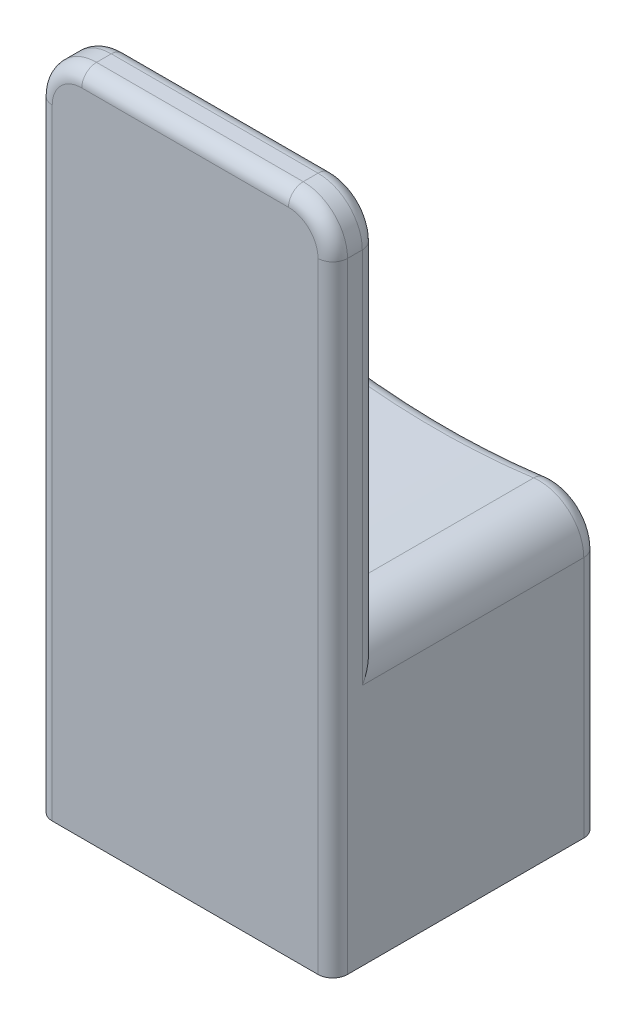
SolidWorks part; units mm, degrees
ref_plane "前视基准面" through (0, 0, 0) normal (0, 0, 1) x (1, 0, 0)
ref_plane "上视基准面" through (0, 0, 0) normal (0, 1, 0) x (1, 0, 0)
ref_plane "右视基准面" through (0, 0, 0) normal (1, 0, 0) x (0, 0, -1)
other "Configuration Table"
sketch "草图1" plane through (0, 0, 0) normal (0, 1, 0) x (1, 0, 0)
  circle A0 centre (0, 0) radius 3.9
  point P2 (1.8977, -1.4542)
  dimension "D1" = 7.8
extrude "凸台-拉伸1" add sketch "草图1" along normal blind 3.5
sketch "草图2" plane through (0, 3.5, 0) normal (0, 1, 0) x (1, 0, 0)
  line L1 (10, -7.5) -> (-10, -7.5)
  line L2 (10, -7.5) -> (10, 7.5)
  line L3 (10, 7.5) -> (-10, 7.5)
  line L4 (-10, -7.5) -> (-10, 7.5)
  line L5 (10, -7.5) -> (-10, 7.5) construction
  line L6 (10, 7.5) -> (-10, -7.5) construction
  point P0 (0, 0)
  dimension "D1" = 20
  dimension "D2" = 15
extrude "凸台-拉伸2" add sketch "草图2" along normal blind 20
sketch "草图3" plane through (0, 0, -7.5) normal (0, 0, -1) x (-1, 0, 0)
  line L0 (10, 23.5) -> (0, 20.5)
  line L1 (-10, 23.5) -> (10, 23.5) construction
  line L2 (0, 20.5) -> (-10, 23.5)
  line L3 (-10, 23.5) -> (-10, 3.5) construction
  line L4 (10, 23.5) -> (-10, 23.5)
  point P4 (0, 0)
  point P8 (0, 18.0324)
  point P9 (-10, 23.5)
  dimension "D1" = 3
extrude "切除-拉伸1" cut sketch "草图3" against normal through all
fillet "圆角1" radius 50 1 edges at (0, 20.5, 0)
fillet "圆角2" radius 3 2 edges at (-10, 23.5, 0) (10, 23.5, 0)
sketch "草图5" plane through (0, 0, 7.5) normal (0, 0, 1) x (1, 0, 0)
  line L0 (-10, 3.5) -> (10, 3.5) construction
  line L1 (-10, 3.5) -> (10, 3.5)
  line L2 (-10, 3.5) -> (-10, 48.5)
  line L3 (-10, 48.5) -> (10, 48.5)
  line L4 (10, 3.5) -> (10, 48.5)
  line L5 (10, 19.9541) -> (10, 3.5) construction
  line L6 (-10, 19.9541) -> (-10, 3.5) construction
  point P6 (0, 0)
  point P9 (-8.1271, 3.5)
  dimension "D1" = 45
extrude "凸台-拉伸3" add sketch "草图5" along normal blind 3
fillet "圆角4" radius 3 2 edges at (-10, 48.5, 9) (10, 48.5, 9)
fillet "圆角5" radius 1 10 edges at (10, 24.5, 10.5) (9.1213, 47.6213, 10.5) (-10, 24.5, 10.5) (-9.1213, 47.6213, 10.5) (10, 32.727, 7.5) (9.1213, 47.6213, 7.5) (-10, 32.727, 7.5) (-9.1213, 47.6213, 7.5) (0, 48.5, 10.5) (0, 48.5, 7.5)
fillet "圆角6" radius 1 5 edges at (-10, 11.727, -7.5) (-8.9763, 22.2112, -7.5) (10, 11.727, -7.5) (8.9763, 22.2112, -7.5) (0, 22.4898, -7.5)
